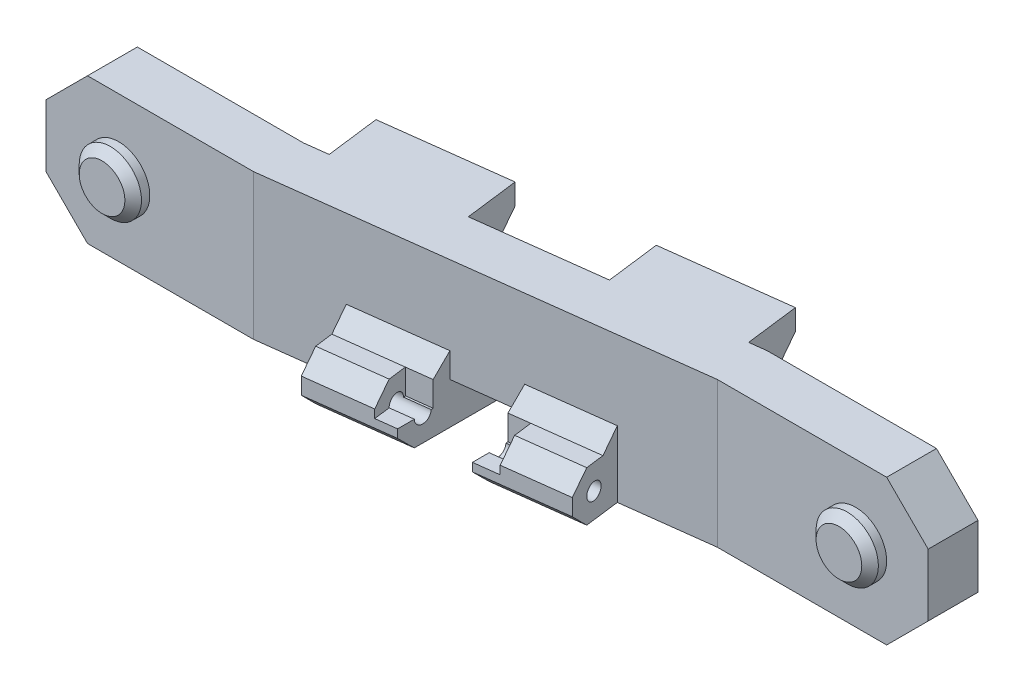
SolidWorks part; units mm, degrees
note: The reader was unsure of these and kept them because the rebuilt part matched: shared geometry of "Sketch1<8>", "Sketch1<10>".
ref_plane "Front Plane" through (0, 0, 0) normal (0, 0, 1) x (1, 0, 0)
ref_plane "Top Plane" through (0, 0, 0) normal (0, 1, 0) x (1, 0, 0)
ref_plane "Right Plane" through (0, 0, 0) normal (1, 0, 0) x (0, 0, -1)
sketch "Sketch1" plane through (0, 0, 0) normal (0, 1, 0) x (1, 0, 0)
  line L0 (-20, -1.25) -> (-9.9216, -1.25) construction
  line L5 (-9.9216, -1.25) -> (9.9216, 1.25) construction
  line L6 (9.9216, 1.25) -> (20, 1.25) construction
  line L7 (-20, -2.45) -> (-20, -0.05)
  line L8 (20, 2.45) -> (20, 0.05)
  line L9 (-20, -0.05) -> (-10, -0.05)
  line L11 (-10, -0.05) -> (9.8431, 2.45)
  line L15 (9.8431, 2.45) -> (20, 2.45)
  line L16 (-20, -2.45) -> (-10, -2.45)
  line L17 (-10, -2.45) -> (9.8431, 0.05)
  line L18 (9.8431, 0.05) -> (20, 0.05)
  line L19 (-10, 2.45) -> (-9.69, -0.0109)
  line L20 (-10, -2.45) -> (-9.6875, -4.9304)
  line L21 (9.8431, 4.95) -> (9.8431, 2.45) construction
  line L22 (-12, -2.45) -> (-12, -4.95)
  line L23 (12, 0.05) -> (12, -2.45)
  line L24 (-12, -4.95) -> (-9.8431, -4.95)
  line L25 (-9.8431, -4.95) -> (10, -2.45)
  line L26 (10, -2.45) -> (12, -2.45)
  line L29 (-12, -0.05) -> (-12, 2.45)
  line L30 (-12, 2.45) -> (-10, 2.45)
  line L33 (9.8431, 4.95) -> (12, 4.95)
  line L34 (12, 4.95) -> (12, 2.45)
  line L35 (-10, 2.45) -> (9.8431, 4.95)
  line L40 (-5.7213, -4.4307) -> (-5.7213, 0.4891) construction
  line L41 (5.5645, -0.4891) -> (5.5645, 4.4109) construction
  line L42 (-10, -0.05) -> (-10, 2.45) construction
  line L43 (-1.91, 3.4692) -> (-1.6, 1.0083)
  line L44 (1.6, 3.9115) -> (1.91, 1.4505)
  line L45 (9.8431, 2.45) -> (9.5331, 4.9109)
  line L46 (10, -2.45) -> (9.6875, 0.0304)
  line L47 (1.6, -0.9885) -> (1.9125, -3.4689)
  line L48 (-5.7213, -4.4307) -> (-6.0338, -1.9503)
  line L49 (-9.845, 1.2195) -> (-6.0748, 1.6945) construction
  line L50 (5.9179, 3.2055) -> (9.6881, 3.6805) construction
  line L51 (5.5645, -0.4891) -> (5.877, -2.9695)
  line L54 (-20, -2.45) -> (-20, -15.0342) construction
  line L55 (-1.6, -3.9115) -> (-1.9125, -1.4311)
  line L56 (-5.9198, 0.4641) -> (-6.2298, 2.925)
  line L57 (-1.6, 3.5083) -> (-1.6, -3.9115)
  line L58 (1.6, 3.9115) -> (1.6, -3.5083)
  line L60 (5.5645, 4.4109) -> (5.8745, 1.95) construction
  line L61 (-10, -0.05) -> (-10, -2.45) construction
  line L65 (-6.0314, 2.95) -> (-5.7213, 0.4891) construction
  line L67 (5.7629, 4.4359) -> (6.0729, 1.975)
  line L69 (-20, -15.0342) -> (20, -15.0342) construction
  line L70 (20, -15.0342) -> (20, 0.05) construction
  line L73 (-5.8776, -3.1905) -> (-9.8438, -3.6902) construction
  line L75 (0, -15.0342) -> (0, 0) construction
  line L76 (-9.8438, -3.6902) -> (-12, -3.7) construction
  line L77 (9.8438, -1.2098) -> (12, -1.2) construction
  point P7 (-20, -1.25)
  point P11 (20, 1.25)
  point P26 (0, 0)
  dimension "D1" = 2.5
  dimension "D2" = 3.8
  dimension "D3" = 2.4
  dimension "D4" = 2.5
  dimension "D5" = 3.8
  dimension "D6" = 20
  dimension "D7" = 40
  dimension "D8" = 8
  dimension "D9" = 8
  dimension "D10" = 2.5
  dimension "D11" = 0.2
  dimension "D13" = 0.2
  dimension "D14" = 1.6
  dimension "D15" = 1.6
extrude "Boss-Extrude4" add sketch "Sketch1" along normal blind 2.4
extrude "Boss-Extrude5" add sketch "Sketch1<8>" along normal offset from surface (7 mm away) 4.6 contours L57 L11 L9 L7 L16 L17 | L11 L58 L17 L18 L8 L15 | L58 L11 L57 L17 up to face at (-7.9599, 2.4, -1.457) offset beyond the face yes
sketch "Sketch1<8>" plane through (0, 0, 0) normal (0, 1, 0) x (1, 0, 0) same geometry as "Sketch1"
sketch "Sketch2" plane through (0, 0, 2.45) normal (0, 0, 1) x (1, 0, 0)
  line L0 (-20, 7) -> (-13, 0) construction
  line L1 (-20, 7) -> (-13, 7)
  line L2 (-20, 7) -> (-20, 0)
  line L3 (-20, 0) -> (-13, 0)
  line L4 (-13, 7) -> (-13, 0)
  line L5 (-20, 0) -> (-13, 7) construction
  line L6 (-20, 0) -> (-10, 0) construction
  line L21 (-16.5, 5.2321) -> (-18, 4.366) construction
  line L22 (-20, 7) -> (-20, 0) construction
  line L23 (-18, 4.366) -> (-18, 2.634) construction
  line L24 (-18, 2.634) -> (-16.5, 1.7679) construction
  line L26 (-16.5, 1.7679) -> (-15, 2.634) construction
  line L27 (-15, 2.634) -> (-15, 4.366) construction
  line L28 (-20, 7) -> (-10, 7) construction
  line L29 (-15, 4.366) -> (-16.5, 5.2321) construction
  circle A1 centre (-16.5, 3.5) radius 1.5
  dimension "D1" = 3
  dimension "D3" = 0
  dimension "D4" = 0
sketch "Sketch3" plane through (0, 0, -0.05) normal (0, 0, 1) x (1, 0, 0)
  line L0 (13, 0) -> (20, 7) construction
  line L1 (13, 0) -> (20, 0)
  line L2 (13, 0) -> (13, 7)
  line L3 (13, 7) -> (20, 7)
  line L4 (20, 0) -> (20, 7)
  line L5 (13, 7) -> (20, 0) construction
  line L6 (9.8431, 0) -> (20, 0) construction
  line L21 (9.8431, 7) -> (20, 7) construction
  line L22 (20, 7) -> (20, 0) construction
  line L23 (16.5, 5.2321) -> (15, 4.366) construction
  line L24 (15, 4.366) -> (15, 2.634) construction
  line L25 (15, 2.634) -> (16.5, 1.7679) construction
  line L26 (16.5, 1.7679) -> (18, 2.634) construction
  line L27 (18, 2.634) -> (18, 4.366) construction
  line L28 (18, 4.366) -> (16.5, 5.2321) construction
  circle A1 centre (16.5, 3.5) radius 1.5
  dimension "D1" = 3
  dimension "D3" = 0
  dimension "D4" = 0
extrude "Boss-Extrude8" add sketch "Sketch2" along normal blind 0.8
extrude "Boss-Extrude9" add sketch "Sketch3" along normal blind 0.8
sketch "Sketch4" plane through (0, 0, 0.05) normal (0, 0, -1) x (-1, 0, 0)
  line L0 (13, 0) -> (20, 7) construction
  line L1 (20, 7) -> (13, 7)
  line L2 (20, 7) -> (20, 0)
  line L3 (20, 0) -> (13, 0)
  line L4 (13, 7) -> (13, 0)
  line L5 (13, 7) -> (20, 0) construction
  line L6 (20, 7) -> (20, 0) construction
  line L21 (20, 7) -> (10, 7) construction
  line L22 (20, 0) -> (10, 0) construction
  line L23 (16.5, 5.463) -> (14.8, 4.4815) construction
  line L24 (14.8, 4.4815) -> (14.8, 2.5185) construction
  line L25 (14.8, 2.5185) -> (16.5, 1.537) construction
  line L26 (16.5, 1.537) -> (18.2, 2.5185) construction
  line L27 (18.2, 2.5185) -> (18.2, 4.4815) construction
  line L28 (18.2, 4.4815) -> (16.5, 5.463) construction
  circle A1 centre (16.5, 3.5) radius 1.7
  dimension "D2" = 3.4
  dimension "D3" = 0
sketch "Sketch5" plane through (0, 0, -2.45) normal (0, 0, -1) x (-1, 0, 0)
  line L0 (-20, 7) -> (-13, 0) construction
  line L1 (-20, 7) -> (-13, 7)
  line L2 (-20, 7) -> (-20, 0)
  line L3 (-20, 0) -> (-13, 0)
  line L4 (-13, 7) -> (-13, 0)
  line L5 (-20, 0) -> (-13, 7) construction
  line L6 (-20, 7) -> (-20, 0) construction
  line L21 (-9.8431, 7) -> (-20, 7) construction
  line L22 (-9.8431, 0) -> (-20, 0) construction
  line L23 (-16.5, 5.463) -> (-18.2, 4.4815) construction
  line L24 (-18.2, 4.4815) -> (-18.2, 2.5185) construction
  line L25 (-18.2, 2.5185) -> (-16.5, 1.537) construction
  line L26 (-16.5, 1.537) -> (-14.8, 2.5185) construction
  line L27 (-14.8, 2.5185) -> (-14.8, 4.4815) construction
  line L28 (-14.8, 4.4815) -> (-16.5, 5.463) construction
  circle A1 centre (-16.5, 3.5) radius 1.7
  dimension "D2" = 3.4
  dimension "D3" = 0
extrude "Cut-Extrude3" cut sketch "Sketch4" against normal blind 1.2
extrude "Cut-Extrude4" cut sketch "Sketch5" against normal blind 1.2
chamfer "Chamfer4" distance 2 angle 45 4 edges at (20, 7, -1.25) (20, 0, -1.25) (-20, 7, 1.25) (-20, 0, 1.25)
sketch "Sketch8" plane through (9.9932, 0, -1.259) normal (0.9922, 0, -0.125) x (-0.125, 0, -0.9922)
  line L0 (2.4808, 1.2) -> (2.4808, 0) construction
  line L1 (3.6808, 0) -> (1.2808, 0)
  line L2 (3.6808, 0) -> (3.6808, 2.4)
  line L3 (3.6808, 2.4) -> (1.2808, 2.4)
  line L4 (1.2808, 0) -> (1.2808, 2.4)
  line L5 (2.4808, 1.2) -> (3.6808, 1.2) construction
  line L6 (3.6808, 2.4) -> (3.6808, 0) construction
  line L7 (-2.4808, 1.2) -> (-3.6808, 1.2) construction
  line L8 (2.0808, 1.4309) -> (2.0808, 1.7381)
  line L9 (2.0808, 1.7381) -> (2.8808, 1.7381)
  line L10 (2.4808, 1.6619) -> (2.0808, 1.4309) construction
  line L11 (2.0808, 1.4309) -> (2.0808, 0.9691) construction
  line L12 (2.0808, 0.9691) -> (2.4808, 0.7381) construction
  line L13 (2.4808, 0.7381) -> (2.8808, 0.9691) construction
  line L14 (2.8808, 0.9691) -> (2.8808, 1.4309) construction
  line L15 (2.8808, 1.4309) -> (2.4808, 1.6619) construction
  line L16 (-2.4808, 1.2) -> (-2.4808, 0) construction
  line L17 (-2.8808, 1.7381) -> (-2.0808, 1.7381)
  line L19 (-3.6808, 0) -> (-1.2808, 0)
  line L20 (-3.6808, 0) -> (-3.6808, 2.4)
  line L21 (-3.6808, 2.4) -> (-1.2808, 2.4)
  line L22 (-1.2808, 0) -> (-1.2808, 2.4)
  line L25 (-3.6808, 2.4) -> (-3.6808, 0) construction
  line L26 (2.8808, 1.7381) -> (2.8808, 1.4309)
  line L27 (-2.4808, 1.6619) -> (-2.8808, 1.4309) construction
  line L28 (-2.8808, 1.4309) -> (-2.8808, 0.9691) construction
  line L29 (-2.8808, 0.9691) -> (-2.4808, 0.7381) construction
  line L30 (-2.4808, 0.7381) -> (-2.0808, 0.9691) construction
  line L31 (-2.0808, 0.9691) -> (-2.0808, 1.4309) construction
  line L32 (-2.0808, 1.4309) -> (-2.4808, 1.6619) construction
  line L33 (-2.8808, 1.4309) -> (-2.8808, 1.7381)
  line L35 (-2.0808, 1.4309) -> (-2.0808, 1.7381)
  line L36 (-3.6808, 2.4) -> (-1.1808, 2.4) construction
  line L38 (3.6808, 2.4) -> (3.6808, 0) construction
  line L39 (1.2004, 0) -> (3.6808, 0) construction
  line L40 (1.2004, 2.4) -> (3.6808, 2.4) construction
  circle A0 centre (2.4808, 1.2) radius 0.4
  circle A1 centre (-2.4808, 1.2) radius 0.4
  point P0 (1.8887, 1.2)
  point P12 (-1.8887, 1.2)
  dimension "D2" = 1
  dimension "D1" = 0.8
  dimension "D3" = 1
  dimension "D4" = 1.2
extrude "Cut-Extrude7" cut sketch "Sketch8" against normal up to surface (19.6875 mm away) up to face at (-9.845, 1.2, -1.2195)
extrude "Cut-Extrude10" cut sketch "Sketch1<10>" along normal offset from surface (2 mm away) 2 contours L58 L11 L57 L17 | L58 L35 L57 L11 | L58 L17 L57 L25 up to face at (-0.4825, 0, 0.1082)
sketch "Sketch1<10>" plane through (0, 0, 0) normal (0, 1, 0) x (1, 0, 0) same geometry as "Sketch1"
chamfer "Chamfer6" distance 0.8 angle 45 12 edges at (7.648, 0, -4.6734) (7.648, 2.4, -4.6734) (3.7385, 0, 3.2389) (3.7385, 2.4, 3.2389) (-3.6607, 0, 4.1711) (-3.6607, 2.4, 4.1711) (3.5822, 2.4, 0.7388) (-3.8169, 2.4, 1.671) (-8.1149, 0, -2.6875) (-8.1149, 2.4, -2.6875) (7.958, 2.4, -2.2125) (-7.8049, 2.4, -0.2266)
chamfer "Chamfer7" [suppressed] distance 0.8 angle 45
sketch "Sketch9" plane through (0, 2.4, 0) normal (0, 1, 0) x (1, 0, 0)
  line L0 (-10, 2.45) -> (-9.79, 0.7828)
  line L1 (-9.79, 0.7828) -> (-8.5994, 0.9328)
  line L2 (-1.6, -2.198) -> (-5.9338, -2.744) construction
  line L3 (-8.5994, 0.9328) -> (-8.8094, 2.6)
  line L4 (-1.6, -3.9115) -> (-5.7213, -4.4307) construction
  line L5 (-8.8094, 2.6) -> (-10, 2.45)
  line L6 (-1.6, -2.198) -> (-2.7906, -2.348)
  line L8 (-2.7906, -2.348) -> (-2.5781, -4.0347)
  line L9 (5.6645, -1.2828) -> (1.6, -1.7949) construction
  line L10 (-2.5781, -4.0347) -> (-1.3875, -3.8847)
  line L11 (-1.3875, -3.8847) -> (-1.6, -2.198)
  line L12 (1.6, -3.5083) -> (1.3875, -1.8216)
  line L13 (1.3875, -1.8216) -> (2.5781, -1.6716)
  line L14 (-10, 2.45) -> (-6.2298, 2.925) construction
  line L15 (2.5781, -1.6716) -> (2.7906, -3.3583)
  line L16 (5.7629, 4.4359) -> (9.5331, 4.9109) construction
  line L17 (2.7906, -3.3583) -> (1.6, -3.5083)
  line L18 (9.5331, 4.9109) -> (8.3425, 4.7609)
  line L20 (8.3425, 4.7609) -> (8.5525, 3.0937)
  line L22 (8.5525, 3.0937) -> (9.7431, 3.2437)
  line L23 (9.7431, 3.2437) -> (9.5331, 4.9109)
  line L31 (5.9729, 2.7687) -> (9.7431, 3.2437) construction
  line L32 (9.7431, 3.2437) -> (9.6331, 4.1172) construction
  line L34 (-9.79, 0.7828) -> (-6.0198, 1.2578) construction
  line L35 (-9.9, 1.6563) -> (-9.79, 0.7828) construction
  point P2 (-1.2609, -3.7375)
  point P17 (0, 0)
  point P18 (1.6, -3.5083)
  dimension "D4" = 1.2
extrude "Cut-Extrude11" cut sketch "Sketch9" against normal blind 1.2 and the other way blind 10
sketch "Sketch10" plane through (0, 7, 0) normal (0, 1, 0) x (1, 0, 0)
  line L10 (-10, -0.05) -> (9.8431, 2.45) construction
  line L12 (-6.0198, 1.2578) -> (-6.1298, 2.1313) construction
  line L18 (2.7715, 4.1796) -> (3.0965, 1.6)
  line L21 (-8.8962, 0.0891) -> (-9.2212, 2.6687)
  line L22 (-9.2212, 2.6687) -> (-3.2683, 3.4187)
  line L23 (-3.2683, 3.4187) -> (-2.9433, 0.8391)
  line L24 (-2.9433, 0.8391) -> (-8.8962, 0.0891)
  line L30 (3.0965, 1.6) -> (9.0494, 2.35)
  line L31 (9.0494, 2.35) -> (8.7244, 4.9296)
  line L32 (8.7244, 4.9296) -> (2.7715, 4.1796)
  line L33 (5.8629, 3.6422) -> (5.9729, 2.7687) construction
  dimension "D1" = 6
  dimension "D2" = 2.6
  dimension "D3" = 3
  dimension "D4" = 3
extrude "Boss-Extrude10" add sketch "Sketch10" against normal offset from surface (3.6 mm away) 3.6 up to face at (-0.0392, 7, 0)
chamfer "Chamfer8" distance 2.6 angle 45 2 edges at (-6.2448, 3.4, -3.0437) (5.7479, 3.4, -4.5546)
sketch "Sketch11" plane through (0, 0, 0) normal (0, 0, 1) x (1, 0, 0)
  line L0 (10.059, 31.6467) -> (36.3088, 31.6467) construction
  line L1 (45.8151, 31.6467) -> (70.8151, 31.6467) construction
  line L2 (42.0816, 62.6523) -> (43.1395, 56.6523)
  line L3 (42.0816, 62.6523) -> (39.8977, 68.6523)
  line L4 (39.8977, 68.6523) -> (36.4336, 74.6523)
  line L5 (43.1395, 56.6523) -> (43.1395, 48.6523)
  line L6 (35.3395, 48.6523) -> (35.3395, 55.9699)
  line L7 (35.3395, 55.9699) -> (34.5186, 60.6258)
  line L8 (34.5186, 60.6258) -> (32.8015, 65.3433)
  line L9 (32.8015, 65.3433) -> (27.427, 74.6523)
  line L10 (35.3395, 48.6523) -> (43.1395, 48.6523)
  line L11 (27.427, 74.6523) -> (36.4336, 74.6523)
  circle A0 centre (10.059, 31.6467) radius 25
  circle A1 centre (70.8151, 31.6467) radius 25
  point P6 (38.1657, 71.6523)
  dimension "D1" = 50
  dimension "D2" = 6
  dimension "D3" = 8
  dimension "D4" = 170
  dimension "D5" = 6
  dimension "D6" = 6
  dimension "D7" = 170
  dimension "D8" = 170
  dimension "D9" = 7.8
  dimension "D10" = 7.8
  dimension "D11" = 7.8
  dimension "D12" = 7.8
  dimension "D13" = 7.3176
  dimension "D14" = 4.6559
  dimension "D15" = 4.7175
  dimension "D16" = 9.309
  dimension "D17" = 0.821
  dimension "D18" = 1.717
  dimension "D19" = 5.3746
chamfer "Chamfer9" distance 0.4 angle 45 2 edges at (18, 3.5, 0.75) (-15, 3.5, 3.25)
